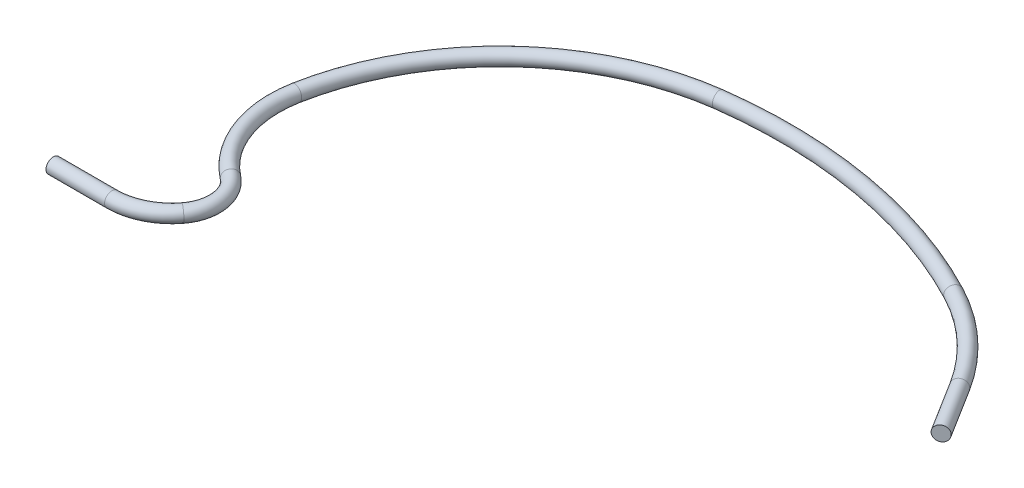
SolidWorks part; units mm, degrees
ref_plane "前视基准面" through (0, 0, 0) normal (0, 0, 1) x (1, 0, 0)
ref_plane "上视基准面" through (0, 0, 0) normal (0, 1, 0) x (1, 0, 0)
ref_plane "右视基准面" through (0, 0, 0) normal (1, 0, 0) x (0, 0, -1)
ref_plane "WireCenter" through (0, 0, 0) normal (0, 1, 0) x (1, 0, 0)
sketch "Circle" plane through (0, 0, 0) normal (0, 1, 0) x (1, 0, 0)
  line L0 (0, 0) -> (-200, 0) construction
  dimension "R" = 200
ref_axis "CenterAxis" through (-200, 0, 0) along (0, 1, 0)
ref_plane "CenterV" through (0, 0, 0) normal (1, 0, 0) x (0, 0, -1)
ref_plane "CenterH" through (0, 0, 0) normal (0, 0, 1) x (1, 0, 0)
sketch "SWireLine" plane through (0, 0, 0) normal (0, 1, 0) x (1, 0, 0)
  line L0 (0, 0) -> (20, 0)
  line L1 (220.1633, 89.2266) -> (230.7706, 72.2712)
  arc A0 (20, 0) -> (36.1809, 7.9397) centre (20, 20.458) ccw
  arc A1 (36.1809, 7.9397) -> (33.7904, 26.6707) centre (25.6202, 16.11) ccw
  arc A2 (33.7904, 26.6707) -> (20, 62.7751) centre (56.5067, 56.0333) cw
  arc A3 (20, 62.7751) -> (94.023, 133.1015) centre (105.4027, 47.0035) cw
  arc A4 (94.023, 133.1015) -> (191.4759, 115.8047) centre (115.4759, -29.2099) cw
  arc A5 (191.4759, 115.8047) -> (220.1633, 89.2266) centre (156.7584, 49.5607) cw
  dimension "D1" = 20
  dimension "D2" = 20
ref_plane "StartFace" through (0, 0, 0) normal (1, 0, 0) x (0, 0, -1)
ref_plane "EndFace" through (230.7706, 0, -72.2712) normal (0.5304, 0, 0.8478) x (0.8478, 0, -0.5304)
ref_plane "EndV" through (198.3534, 0, -124.0892) normal (-0.8478, 0, 0.5304) x (0.5304, 0, 0.8478)
sketch "草图1" plane through (0, 0, 0) normal (1, 0, 0) x (0, 0, -1)
  circle A0 centre (0, 0) radius 2.5
  dimension "D1" = 5
sweep "Wire" add profiles "草图1" path "SWireLine"
